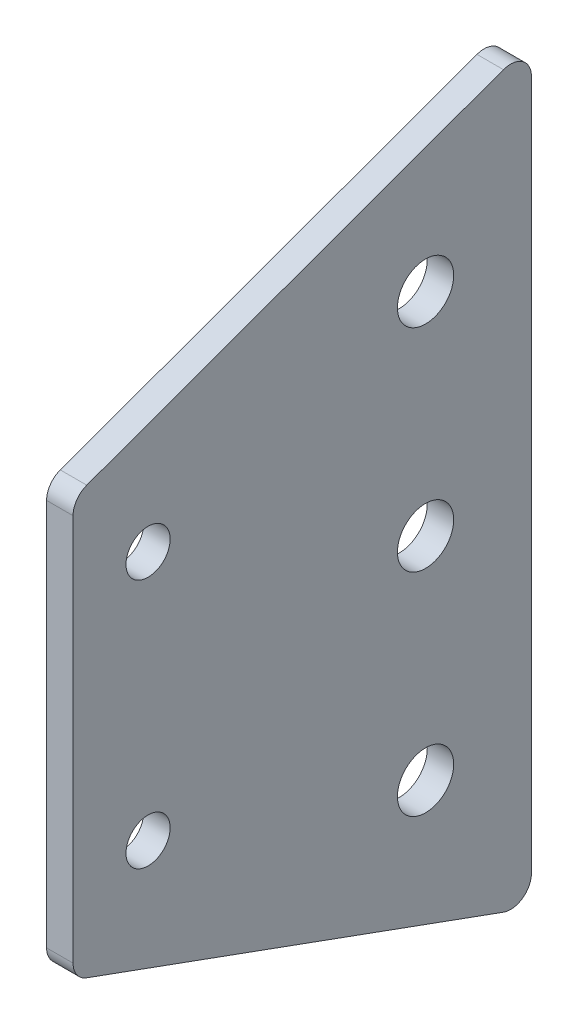
SolidWorks part; units mm, degrees
material "6061 Alloy"
ref_plane "Front Plane" through (0, 0, 0) normal (0, 0, 1) x (1, 0, 0)
ref_plane "Top Plane" through (0, 0, 0) normal (0, 1, 0) x (1, 0, 0)
ref_plane "Right Plane" through (0, 0, 0) normal (1, 0, 0) x (0, 0, -1)
sketch "Sketch1" plane through (0, 0, 0) normal (1, 0, 0) x (0, 0, -1)
  line L0 (-27.5, 0) -> (27.5, 0) construction
  line L1 (-27.5, 25) -> (-27.5, -25)
  line L3 (27.5, 45) -> (27.5, -45)
  line L4 (-27.5, 25) -> (27.5, 45)
  line L5 (-27.5, -25) -> (27.5, -45)
  dimension "D1" = 50
  dimension "D4" = 55
  dimension "D5" = 90
extrude "1/8 Inch Sheet" add sketch "Sketch1" along normal mid plane 3.175
hole_wizard "M5 Clearance Hole1" positions "Sketch5" profile "Sketch6" hole size "M5" standard "ANSI Metric" end condition up to next
sketch "Sketch5" plane through (1.5875, 0, 0) normal (1, 0, 0) x (0, 0, -1)
  line L0 (0, 0) -> (-27.5, 0) construction
  line L1 (-27.5, 25) -> (-27.5, -25) construction
  line L3 (-18.5, 15) -> (-18.5, 0) construction
  line L5 (-18.5, 0) -> (-18.5, -15) construction
  point P0 (-18.5, 15)
  point P2 (-18.5, -15)
  dimension "D1" = 9
  dimension "D2" = 15
sketch "Sketch6" plane through (1.5875, 15, 18.5) normal (0, 1, 0) x (0, 0, -1)
  line L0 (0, 0) -> (0, 3.175)
  line L1 (0, 3.175) -> (2.65, 3.175)
  line L2 (2.65, 3.175) -> (2.65, 0)
  line L5 (2.65, 0) -> (0, 0)
  line L11 (0, -6.35) -> (0, 107.95) construction
  dimension "Thru Hole Dia." = 5.3
  dimension "Thru Hole Depth" = 3.175
hole_wizard "1/4 in Clearance Hole1" positions "Sketch3" profile "Sketch4" hole size "1/4" standard "ANSI Inch" end condition up to next
sketch "Sketch3" plane through (1.5875, 0, 0) normal (1, 0, 0) x (0, 0, -1)
  line L0 (0, 0) -> (14.8, 0) construction
  line L1 (14.8, 0) -> (14.8, 25.4) construction
  line L2 (14.8, 0) -> (14.8, -25.4) construction
  line L5 (27.5, -45) -> (27.5, 45) construction
  point P0 (14.8, 25.4)
  point P2 (14.8, 0)
  point P4 (14.8, -25.4)
  dimension "D2" = 25.4
  dimension "D1" = 12.7
sketch "Sketch4" plane through (1.5875, 25.4, -14.8) normal (0, 1, 0) x (0, 0, -1)
  line L0 (0, 0) -> (0, 3.175)
  line L1 (0, 3.175) -> (3.3782, 3.175)
  line L2 (3.3782, 3.175) -> (3.3782, 0)
  line L5 (3.3782, 0) -> (0, 0)
  line L11 (0, -6.35) -> (0, 107.95) construction
  dimension "Thru Hole Dia." = 6.7564
  dimension "Thru Hole Depth" = 3.175
chamfer "Chamfer 0.5 mm" [suppressed] distance 0.25 angle 45
fillet "Fillet1" radius 2.5 4 edges at (0, 45, -27.5) (0, -45, -27.5) (0, -25, 27.5) (0, 25, 27.5)
equation "\"D1@Sketch3\"= 25.4/2"
